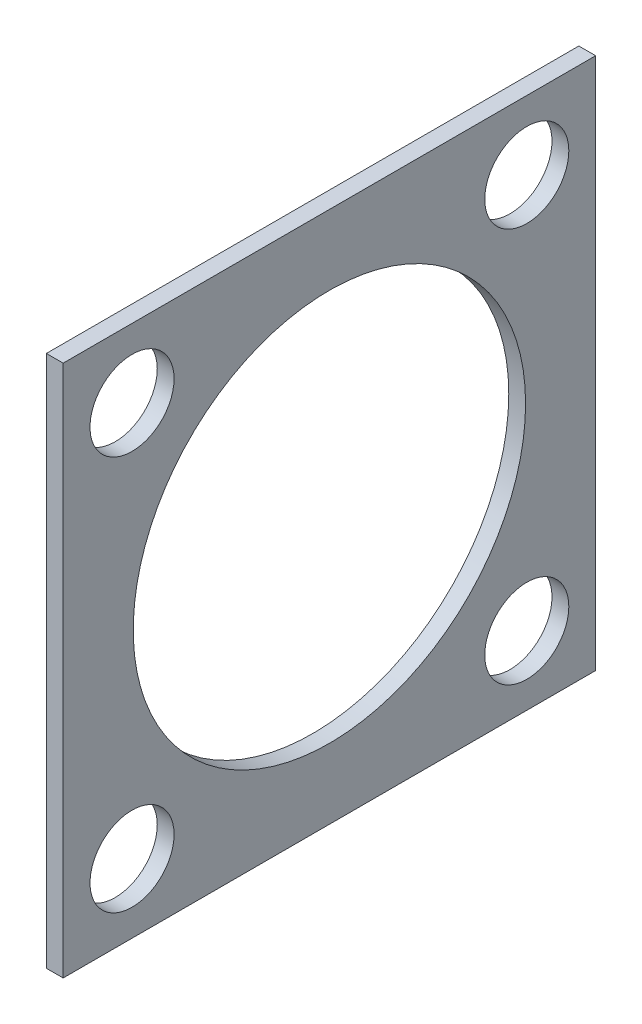
SolidWorks part; units mm, degrees
material "AISI 1020 Acero laminado en frío"
ref_plane "Alzado" through (0, 0, 0) normal (0, 0, 1) x (1, 0, 0)
ref_plane "Planta" through (0, 0, 0) normal (0, 1, 0) x (1, 0, 0)
ref_plane "Vista lateral" through (0, 0, 0) normal (1, 0, 0) x (0, 0, -1)
sketch "Croquis2" plane through (0, 0, 0) normal (1, 0, 0) x (0, 0, -1)
  line L1 (-19, -19) -> (19, -19)
  line L2 (-19, -19) -> (-19, 19)
  line L3 (-19, 19) -> (19, 19)
  line L4 (19, -19) -> (19, 19)
  line L5 (-19, -19) -> (19, 19) construction
  line L6 (-19, 19) -> (19, -19) construction
  line L7 (14.085, 14.085) -> (-14.085, 14.085) construction
  line L8 (14.085, 14.085) -> (14.085, -14.085) construction
  line L9 (14.085, -14.085) -> (-14.085, -14.085) construction
  line L10 (-14.085, 14.085) -> (-14.085, -14.085) construction
  line L11 (14.085, 14.085) -> (-14.085, -14.085) construction
  line L12 (14.085, -14.085) -> (-14.085, 14.085) construction
  circle A0 centre (0, 0) radius 14
  circle A1 centre (-14.085, -14.085) radius 3
  circle A2 centre (-14.085, 14.085) radius 3
  circle A3 centre (14.085, 14.085) radius 3
  circle A4 centre (14.085, -14.085) radius 3
  point P0 (0, 0)
  dimension "D3" = 28
  dimension "D6" = 6
  dimension "D1" = 38
  dimension "D2" = 38
  dimension "D4" = 28.17
  dimension "D5" = 28.17
base flange "Brida base1" sketch "Croquis2" thickness 1.2 reverse thickness direction no parameters "D1"=0.7366
sketch "Líneas de pliegue1" [suppressed] plane through (0, 0, 0) normal (0, 1, 0) x (1, 0, 0)
sketch "Cuadro delimitador1" [suppressed] plane through (0, 0, 0) normal (0, 1, 0) x (1, 0, 0)
sheet metal parameters "Chapa metálica1" thickness 1.2 parameters "D1"=0.7366
flat pattern "Chapa desplegada1" [suppressed]
sketch "Líneas de pliegue2" plane through (0, 0, 0) normal (0, 1, 0) x (1, 0, 0)
sketch3d "Cuadro delimitador2" [suppressed]
  line L0 (19, -19, 0) -> (-19, -19, 0) construction
  line L1 (19, 19, 0) -> (-19, 19, 0) construction
  line L2 (19, -19, 0) -> (19, 19, 0) construction
  line L3 (-19, -19, 0) -> (-19, 19, 0) construction
